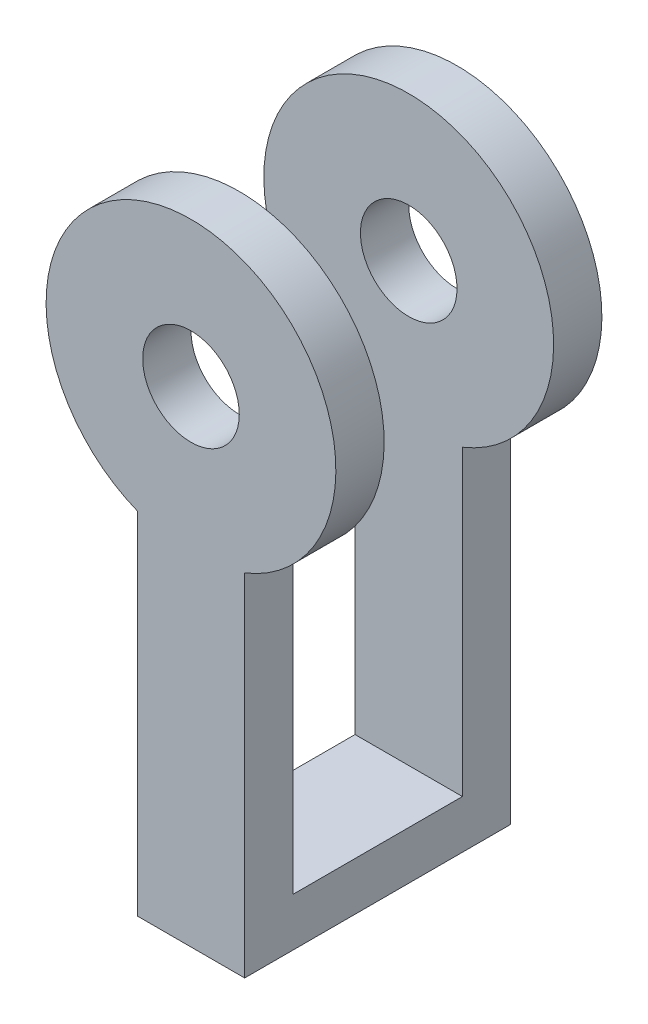
SolidWorks part; units mm, degrees
ref_plane "Спереди" through (0, 0, 0) normal (0, 0, 1) x (1, 0, 0)
ref_plane "Сверху" through (0, 0, 0) normal (0, 1, 0) x (1, 0, 0)
ref_plane "Справа" through (0, 0, 0) normal (1, 0, 0) x (0, 0, -1)
sketch "Эскиз1_fr" plane through (0, 0, 0) normal (0, 0, 1) x (1, 0, 0)
  line L2 (-5.5576, -13.9324) -> (-5.5576, -62.6423)
  line L3 (-5.5576, -62.6423) -> (5.5576, -62.6423)
  line L4 (5.5576, -13.9324) -> (5.5576, -62.6423)
  circle A0 centre (0, 0) radius 5
  arc A1 (5.5576, -13.9324) -> (-5.5576, -13.9324) centre (0, 0) ccw
  circle A3 centre (0, 0) radius 15 construction
  point P9 (14.3446, 4.3856)
  dimension "D1" = 10
  dimension "D2" = 30
sketch "Эскиз3" plane through (0, 0, 0) normal (1, 0, 0) x (0, 0, -1)
  line L0 (-58.3945, -50.2531) -> (-85.9381, -50.2531)
  line L1 (-85.9381, -50.2531) -> (-85.9381, 27.5805)
  line L2 (-58.3945, -50.2531) -> (-58.3945, 27.5805)
  line L3 (-80.9381, -45.2531) -> (-80.9381, 27.5805)
  line L4 (-63.3945, -45.2531) -> (-80.9381, -45.2531)
  line L5 (-63.3945, -45.2531) -> (-63.3945, 27.5805)
  line L6 (-85.9381, 27.5805) -> (-80.9381, 27.5805)
  line L7 (-63.3945, 27.5805) -> (-58.3945, 27.5805)
  point P3 (-72.1663, -50.2531)
extrude "Бобышка-Вытянуть5" add sketch "Эскиз1_fr" along normal blind 30 and the other way blind 30
extrude "Бобышка-Вытянуть6" add sketch "Эскиз3" along normal blind 20 and the other way blind 20 separate body
move or copy body "Тело-Переместить/Копировать1" bodies to move or copy 114 copy no translate (0, 0, -70)
combine bodies "Соединить1" operation type common bodies to combine 112 115
